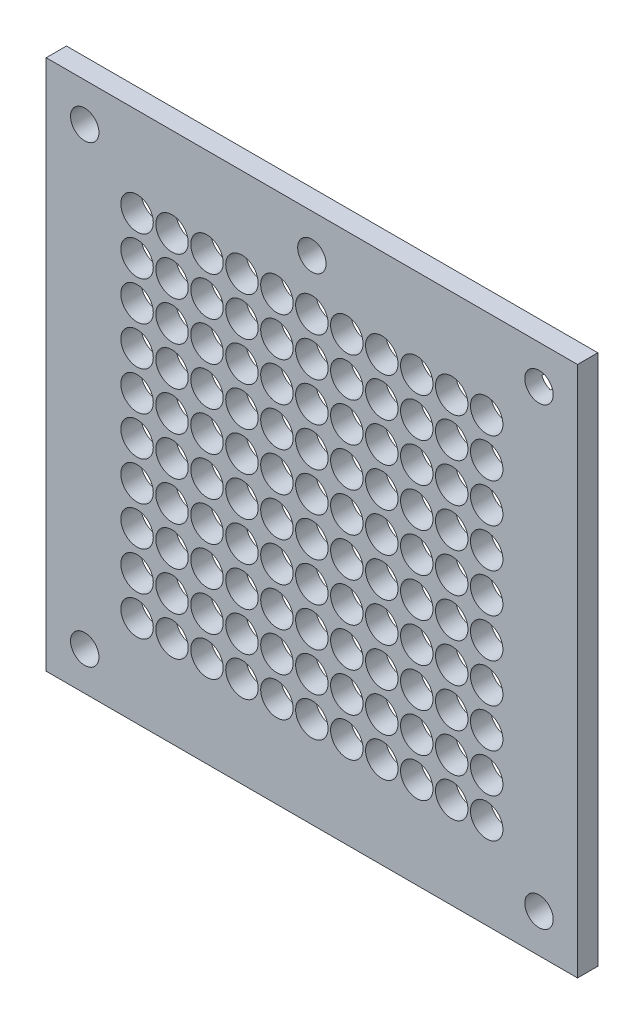
SolidWorks part; units mm, degrees
ref_plane "Ebene vorne" through (0, 0, 0) normal (0, 0, 1) x (1, 0, 0)
ref_plane "Ebene oben" through (0, 0, 0) normal (0, 1, 0) x (1, 0, 0)
ref_plane "Ebene rechts" through (0, 0, 0) normal (1, 0, 0) x (0, 0, -1)
sketch "Skizze2" plane through (0, 0, 0) normal (0, 0, 1) x (1, 0, 0)
  line L0 (-65.5, 65.5) -> (-65.5, -65.5) construction
  line L1 (-65.5, -65.5) -> (65.5, -65.5) construction
  line L2 (65.5, 65.5) -> (-65.5, 65.5) construction
  line L3 (65.5, -65.5) -> (65.5, 65.5) construction
  line L4 (-65.5, 65.5) -> (-65.5, -65.5)
  line L5 (-65.5, -65.5) -> (65.5, -65.5)
  line L6 (65.5, 65.5) -> (-65.5, 65.5)
  line L7 (65.5, -65.5) -> (65.5, 65.5)
extrude "Aufsatz-Linear austragen1" add sketch "Skizze2" along normal blind 5
sketch "Skizze3" plane through (0, 0, 0) normal (0, 0, -1) x (-1, 0, 0)
  line L0 (0, 65.5) -> (0, 0) construction
  line L1 (-65.5, 65.5) -> (65.5, 65.5) construction
  line L2 (-67.5, 67.5) -> (67.5, 67.5) construction
  circle A0 centre (0, 56) radius 3.5
  dimension "D1" = 7
  dimension "D2" = 11.5
extrude "Schnitt-Linear austragen1" cut sketch "Skizze3" against normal up to surface (5 mm away) up to face at (0, 0, 5)
sketch "Skizze4" plane through (0, 0, 0) normal (0, 0, -1) x (-1, 0, 0)
  line L0 (0, 0) -> (0, 65.5) construction
  line L1 (-65.5, 65.5) -> (65.5, 65.5) construction
  line L2 (-67.5, 67.5) -> (67.5, 67.5) construction
  circle A0 centre (0, 43.5) radius 4
  dimension "D1" = 8
  dimension "D2" = 24
extrude "Schnitt-Linear austragen2" cut sketch "Skizze4" against normal up to surface (5 mm away) up to face at (3.5, 56, 5)
pattern_linear "Lineares Muster1" count 6 spacing 8.62 along (1, 0, 0) count 10 spacing 9.6111 along (0, -1, 0) of "Schnitt-Linear austragen2"
pattern_linear "Lineares Muster2" count 6 spacing 8.62 along (-1, 0, 0) count 10 spacing 9.6111 along (0, -1, 0) skipping (0, 1), (0, 2), (0, 3), (0, 4), (0, 5), (0, 6), (0, 7), (0, 8), (0, 9) of "Schnitt-Linear austragen2"
sketch "Skizze5" plane through (0, 0, 0) normal (0, 0, -1) x (-1, 0, 0)
  line L0 (-67.5, -67.5) -> (-67.5, 67.5) construction
  line L1 (-67.5, 67.5) -> (67.5, 67.5) construction
  line L2 (67.5, 67.5) -> (67.5, -67.5) construction
  line L3 (67.5, -67.5) -> (-67.5, -67.5) construction
  circle A0 centre (-50, 50) radius 5.5
  circle A1 centre (50, 50) radius 5.5
  circle A2 centre (-50, -50) radius 5.5
  circle A3 centre (50, -50) radius 5.5
  dimension "D1" = 11
  dimension "D3" = 17.5
  dimension "D4" = 11
  dimension "D5" = 17.5
  dimension "D6" = 17.5
  dimension "D7" = 11
  dimension "D8" = 11
  dimension "D9" = 17.5
  dimension "D10" = 17.5
  dimension "D11" = 17.5
  dimension "D12" = 17.5
  dimension "D2" = 17.5
extrude "Schnitt-Linear austragen3" cut sketch "Skizze5" against normal blind 1
sketch "Skizze6" plane through (0, 0, 0) normal (0, 0, -1) x (-1, 0, 0)
  line L0 (-67.5, -67.5) -> (-67.5, 67.5) construction
  line L1 (-67.5, 67.5) -> (67.5, 67.5) construction
  line L2 (67.5, -67.5) -> (-67.5, -67.5) construction
  line L3 (67.5, 67.5) -> (67.5, -67.5) construction
  circle A0 centre (-56, 56) radius 3.5
  circle A1 centre (-56, -56) radius 3.5
  circle A2 centre (56, -56) radius 3.5
  circle A3 centre (56, 56) radius 3.5
  dimension "D1" = 7
  dimension "D2" = 11.5
  dimension "D3" = 11.5
  dimension "D4" = 7
  dimension "D5" = 7
  dimension "D6" = 7
  dimension "D7" = 11.5
  dimension "D8" = 11.5
  dimension "D9" = 11.5
  dimension "D11" = 11.5
  dimension "D12" = 11.5
  dimension "D10" = 11.5
extrude "Schnitt-Linear austragen4" cut sketch "Skizze6" against normal up to surface (5 mm away) up to face at (-39.1, -43, 5)
sketch "Skizze7" plane through (0, 0, 1) normal (0, 0, -1) x (-1, 0, 0)
  circle A0 centre (-50, 50) radius 3
  circle A1 centre (50, 50) radius 3
  circle A2 centre (50, -50) radius 3
  circle A3 centre (-50, -50) radius 3
extrude "Schnitt-Linear austragen5" cut sketch "Skizze7" against normal blind 1.2
